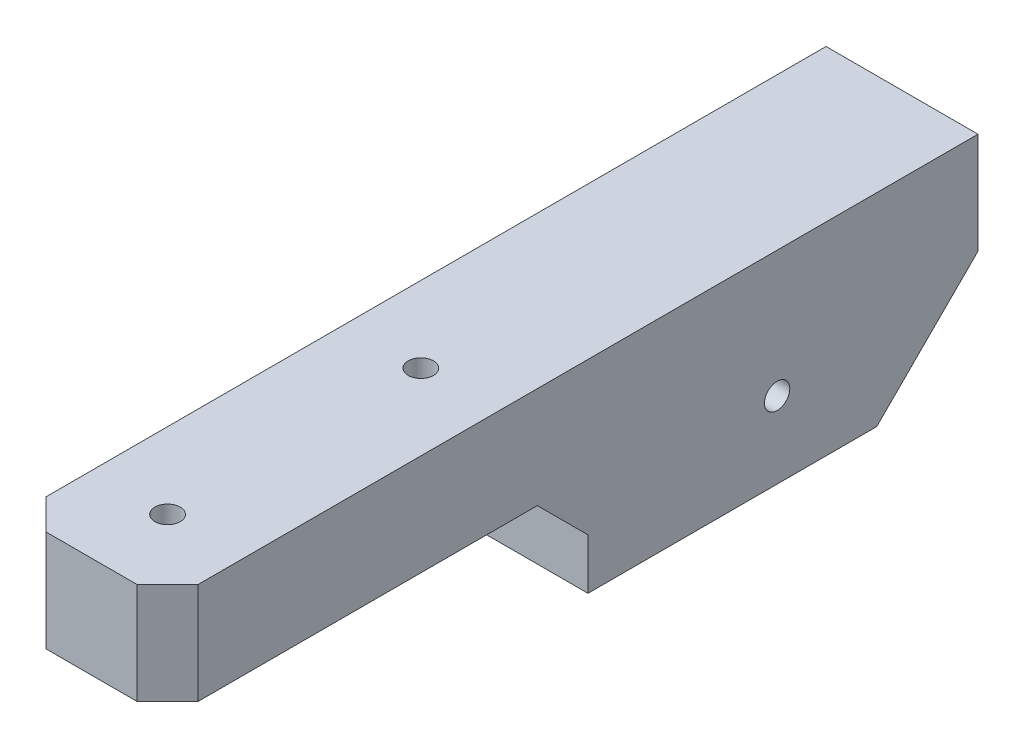
SolidWorks part; units mm, degrees
ref_plane "Ön Düzlem" through (0, 0, 0) normal (0, 0, 1) x (1, 0, 0)
ref_plane "Üst Düzlem" through (0, 0, 0) normal (0, 1, 0) x (1, 0, 0)
ref_plane "Sağ Düzlem" through (0, 0, 0) normal (1, 0, 0) x (0, 0, -1)
sketch "Çizim2" plane through (0, 0, 0) normal (1, 0, 0) x (0, 0, -1)
  line L0 (-80, 20) -> (80, 20)
  line L1 (80, 20) -> (80, 0)
  line L2 (80, 0) -> (60, -20)
  line L3 (60, -20) -> (3, -20)
  line L4 (3, -20) -> (3, -10)
  line L5 (3, -10) -> (-7, 0)
  line L6 (-7, 0) -> (-80, 0)
  line L7 (-80, 0) -> (-80, 20)
  dimension "D1" = 20
  dimension "D2" = 160
  dimension "D3" = 20
  dimension "D4" = 40
  dimension "D5" = 135
  dimension "D6" = 135
  dimension "D7" = 10
  dimension "D8" = 20
  dimension "D9" = 80
  dimension "D10" = 57
extrude "Yükseklik-Ekstrüzyon2" add sketch "Çizim2" along normal blind 30
sketch "Çizim3" plane through (0, 20, 0) normal (0, 1, 0) x (1, 0, 0)
  line L0 (30, -80) -> (0, -80) construction
  line L1 (0, 80) -> (0, -80) construction
  circle A0 centre (15, -15) radius 2.5
  circle A1 centre (15, -65) radius 2.5
  dimension "D1" = 15
  dimension "D2" = 50
  dimension "D3" = 5
  dimension "D4" = 5
  dimension "D5" = 15
extrude "Kes-Ekstrüzyon1" cut sketch "Çizim3" against normal blind 30
chamfer "Pah1" distance 6 angle 45 2 edges at (0, 10, 80) (30, 10, 80)
sketch "Çizim5" plane through (0, -3.5, 3.5) normal (0, -0.7071, 0.7071) x (1, 0, 0)
  circle A0 centre (15, -32) radius 10
  dimension "D1" = 20
  dimension "D2" = 32
  dimension "D3" = 15
extrude "Kes-Ekstrüzyon2" cut sketch "Çizim5" against normal blind 30 and the other way blind 30
sketch "Çizim6" plane through (0, 17.7132, -17.7132) normal (0, -0.7071, 0.7071) x (1, 0, 0)
  circle A0 centre (15, -32) radius 10
  dimension "D1" = 20
extrude "Kes-Ekstrüzyon3" cut sketch "Çizim6" against normal blind 15
sketch "Çizim7" plane through (30, 0, 0) normal (1, 0, 0) x (0, 0, -1)
  line L0 (43.8762, 12.7635) -> (58.0183, -1.3787) construction
  line L1 (43.8762, 12.7635) -> (50.9472, 5.6924)
  line L2 (43.8762, 12.7635) -> (11.1127, -20)
  line L3 (3, -20) -> (60, -20) construction
  circle A0 centre (40.3406, -4.9142) radius 2.5
  dimension "D1" = 5
  dimension "D3" = 10
  dimension "D2" = 15
  dimension "D4" = 10
extrude "Kes-Ekstrüzyon4" cut sketch "Çizim7" against normal blind 48 contours A0 region at (30, -4.9142, -40.3406)
